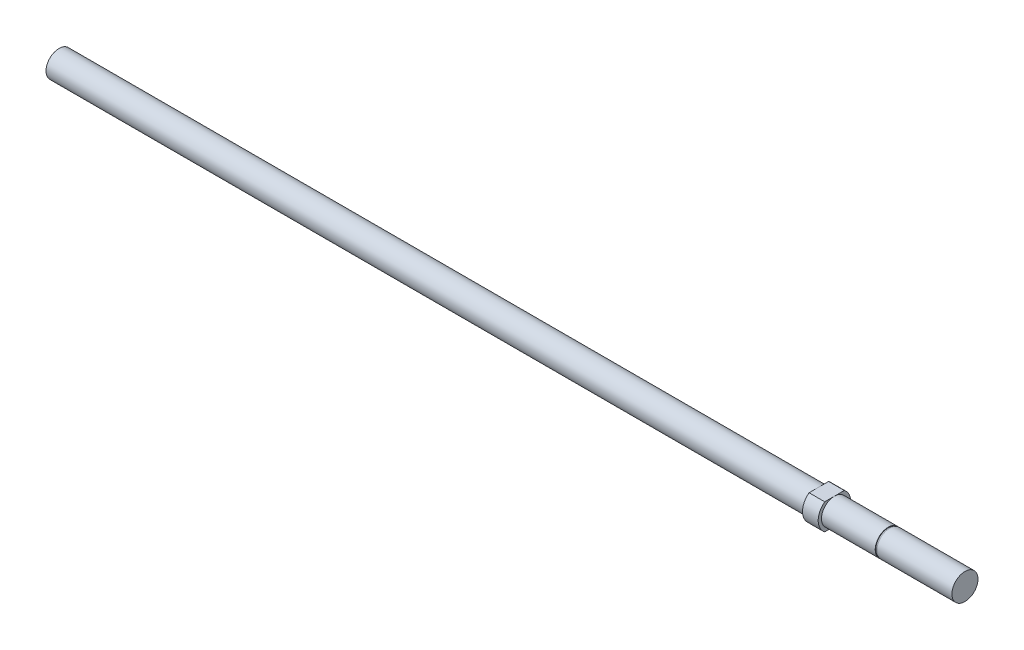
SolidWorks part; units mm, degrees
ref_plane "XY" through (0, 0, 0) normal (0, 0, 1) x (1, 0, 0)
ref_plane "XZ" through (0, 0, 0) normal (0, 1, 0) x (1, 0, 0)
ref_plane "YZ" through (0, 0, 0) normal (1, 0, 0) x (0, 0, -1)
ref_axis "X" through (-230.8288, 0, 0) along (1, 0, 0)
ref_axis "Y" through (0, -3.4925, 0) along (0, 1, 0)
ref_axis "Z" through (0, 0, 4.3656) along (0, 0, -1)
sketch "Sketch1" plane through (0, 0, 0) normal (0, 0, 1) x (1, 0, 0)
  line L0 (0, 0) -> (-220.472, 0)
  line L1 (-220.472, 0) -> (-220.472, 3.175)
  line L2 (-220.472, 3.175) -> (-35.56, 3.175)
  line L3 (-35.56, 3.175) -> (-35.56, 3.9687)
  line L4 (-35.56, 3.9687) -> (-31.75, 3.9687)
  line L5 (-31.75, 3.9687) -> (-31.75, 3.175)
  line L6 (-31.75, 3.175) -> (-18.669, 3.175)
  line L7 (0, 3.175) -> (0, 0)
  line L8 (-18.669, 3.175) -> (-18.669, 3.0226)
  line L9 (-18.669, 3.0226) -> (-18.288, 3.0226)
  line L10 (-18.288, 3.0226) -> (-18.288, 3.175)
  line L11 (-18.288, 3.175) -> (0, 3.175)
  dimension "D1" = 184.912
  dimension "D2" = 3.81
  dimension "D3" = 13.081
  dimension "D4" = 3.175
  dimension "D5" = 3.9688
  dimension "D6" = 3.0226
  dimension "D7" = 0.381
  dimension "D8" = 31.75
revolve "Revolve1" add sketch "Sketch1" angle 360 about L0
sketch "Sketch2" plane through (0, 0, 0) normal (1, 0, 0) x (0, 0, -1)
  line L1 (-3.9688, -3.175) -> (3.9688, -3.175)
  line L2 (-3.9688, -3.175) -> (-3.9688, 3.175)
  line L3 (-3.9688, 3.175) -> (3.9688, 3.175)
  line L4 (3.9688, -3.175) -> (3.9688, 3.175)
  circle A0 centre (0, 0) radius 3.175 construction
  circle A1 centre (0, 0) radius 3.9688 construction
extrude "Cut-Extrude1" cut sketch "Sketch2" against normal through all flip side to cut
sketch "Sketch3" plane through (0, 0, 0) normal (1, 0, 0) x (0, 0, -1)
  circle A0 centre (0, 0) radius 3.175 construction
  circle A1 centre (0, 0) radius 3.175
